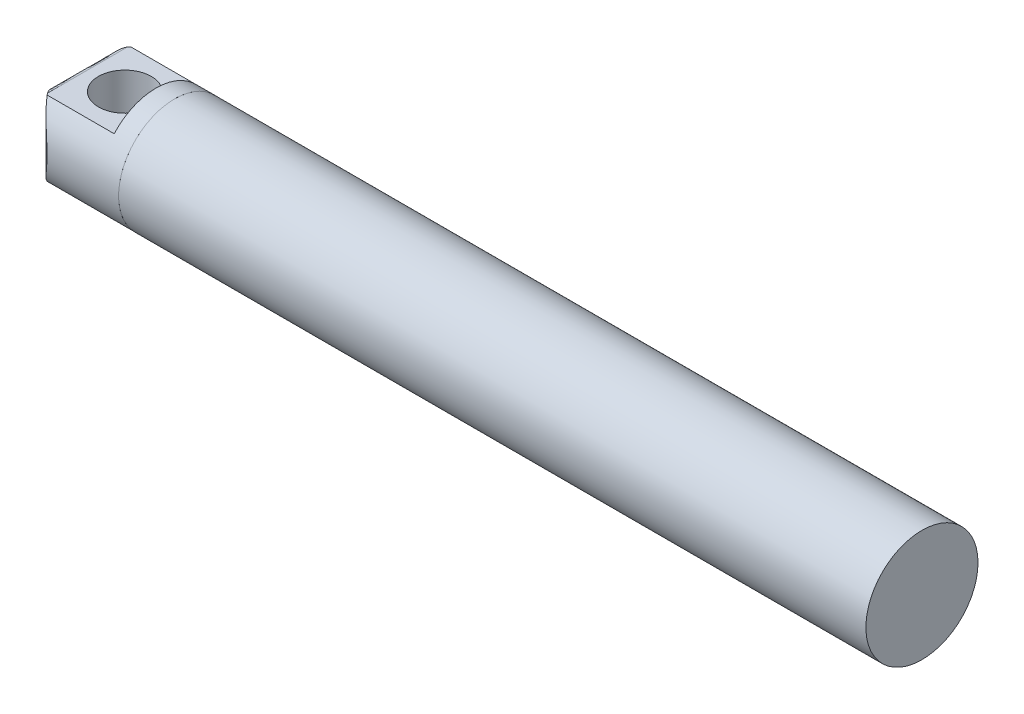
SolidWorks part; units mm, degrees
ref_plane "Front Plane" through (0, 0, 0) normal (0, 0, 1) x (1, 0, 0)
ref_plane "Top Plane" through (0, 0, 0) normal (0, 1, 0) x (1, 0, 0)
ref_plane "Right Plane" through (0, 0, 0) normal (1, 0, 0) x (0, 0, -1)
sketch "Sketch2" plane through (0, 0, 0) normal (1, 0, 0) x (0, 0, -1)
  circle A0 centre (0, 0) radius 4.5
  dimension "D1" = 9
extrude "Boss-Extrude1" add sketch "Sketch2" along normal blind 60
sketch "Sketch3" plane through (0, 0, 0) normal (-1, 0, 0) x (0, 0, 1)
  circle A1 centre (0, 0) radius 4.5
  circle A2 centre (0, 0) radius 4.5
  dimension "D1" = 0
extrude "Boss-Extrude2" add sketch "Sketch3" along normal blind 8 separate body
sketch "Sketch4" plane through (-8, 0, 0) normal (-1, 0, 0) x (0, 0, 1)
  line L1 (-3.3541, 3) -> (3.3541, 3)
  line L2 (-3.3541, 3) -> (-3.3541, -3)
  line L3 (-3.3541, -3) -> (3.3541, -3)
  line L4 (3.3541, 3) -> (3.3541, -3)
  line L5 (-3.3541, 3) -> (3.3541, -3) construction
  line L6 (-3.3541, -3) -> (3.3541, 3) construction
  circle A0 centre (0, 0) radius 4.5 construction
  circle A2 centre (0, 0) radius 4.5
  circle A3 centre (0, 0) radius 4.5
  point P0 (0, 0)
  circle M5 centre (0, 0) radius 4.5
  dimension "D1" = 6
  dimension "D2" = 0
extrude "Cut-Extrude1" cut sketch "Sketch4" against normal offset from surface (6.5 mm away) 1.5 contours L1 M5 | L3 M5 region at (-8, 3.6095, 0) region at (-8, -3.6095, 0) up to face at (0, 0, 4.5)
sketch "Sketch5" plane through (0, -3, 0) normal (0, -1, 0) x (1, 0, 0)
  line L0 (0, 0) -> (-8, 0) construction
  line L1 (-8, -3.3541) -> (-8, 3.3541) construction
  circle A0 centre (-4, 0) radius 2.125
  dimension "D1" = 4.25
  dimension "D2" = 4
extrude "Cut-Extrude2" cut sketch "Sketch5" against normal through all
fillet "Fillet1" [suppressed] radius 1.5
sketch "Sketch6" plane through (0, -3, 0) normal (0, -1, 0) x (1, 0, 0)
  line L0 (-8, -4.5) -> (-3.5, -4.5) construction
  line L2 (-8, 0) -> (0, 0) construction
  line L4 (-8, -3.3541) -> (-8, 3.3541) construction
  line L5 (-8, 4.5) -> (-3.5, 4.5) construction
  line L6 (-3.5, -4.5) -> (-8, -4.5)
  line L7 (-8, -4.5) -> (-8, 4.5)
  line L8 (-8, 4.5) -> (-3.5, 4.5)
  line L9 (-1.5, 3.3541) -> (-8, 3.3541) construction
  arc A0 (-3.5, -4.5) -> (-3.5, 4.5) centre (-3.5, 0) cw
  point P1 (-6.5, 3.3541)
  dimension "D1" = 1.5
fillet "Fillet2" radius 1 1 edges at (-8, -3, 0) second distance 3 first distance on face at (-4, -3, -2.125)
fillet "Fillet3" radius 1 1 edges at (-8, 3, 0) second distance 3 first distance on face at (-4, 3, -2.125)
sketch "Sketch8" plane through (0, -3, 0) normal (0, -1, 0) x (1, 0, 0)
  line L0 (-8, 0) -> (0, 0) construction
  line L1 (-8, -4.5) -> (-8, 4.5) construction
  line L3 (-8, 4.5) -> (-3.5, 4.5) construction
  line L4 (-3.5, -4.5) -> (-8, -4.5) construction
  line L5 (-5.75, -4.5) -> (-8, -4.5)
  line L6 (-8, -4.5) -> (-8, 4.5)
  line L7 (-8, 4.5) -> (-5.75, 4.5)
  arc A0 (-5.75, -4.5) -> (-5.75, 4.5) centre (-2.375, 0) cw
  line M2 (-1.5, 3.3541) -> (-7, 3.3541)
  line M4 (-7, -3.3541) -> (-1.5, -3.3541)
  dimension "D1" = 2.25
extrude "Cut-Extrude5" cut sketch "Sketch8" against normal through all both and the other way through all contours A0 M4 | L5 A0 L6 M4 | A0 M2 | L6 A0 L7 M2 region at (-7.3567, -3, 3.4249) region at (-7.3567, -3, -3.4249)
